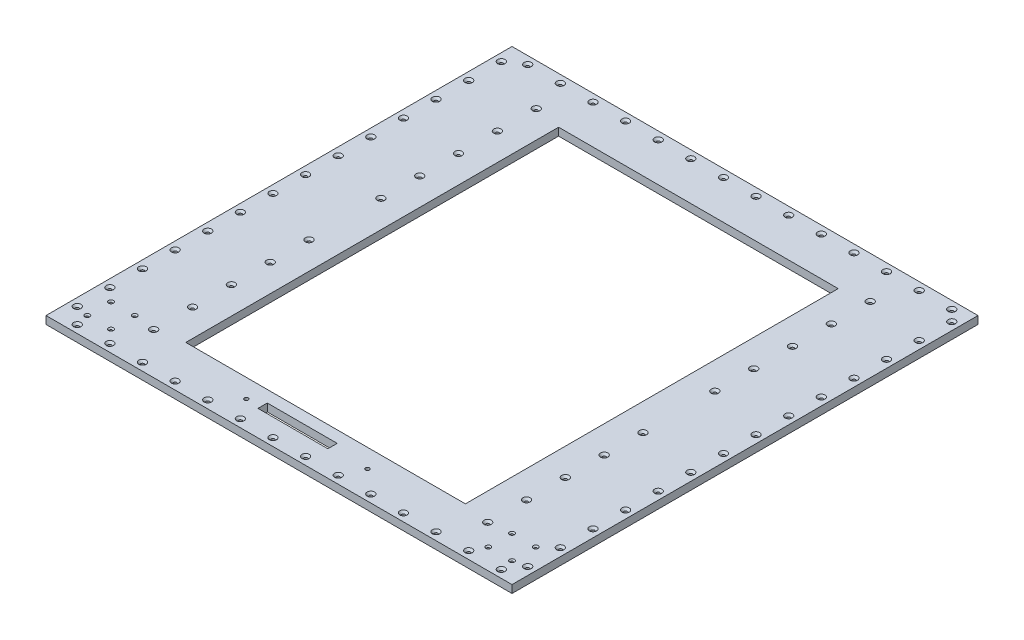
SolidWorks part; units mm, degrees
ref_plane "Płaszczyzna przednia" through (0, 0, 0) normal (0, 0, 1) x (1, 0, 0)
ref_plane "Płaszczyzna górna" through (0, 0, 0) normal (0, 1, 0) x (1, 0, 0)
ref_plane "Płaszczyzna prawa" through (0, 0, 0) normal (1, 0, 0) x (0, 0, -1)
sketch "Sketch1" plane through (0, 0, 0) normal (0, 1, 0) x (1, 0, 0)
  line L1 (0, 0) -> (600, 0)
  line L2 (0, 0) -> (0, 600)
  line L3 (0, 600) -> (600, 600)
  line L4 (600, 0) -> (600, 600)
  line L5 (0, 0) -> (600, 600) construction
  line L6 (0, 600) -> (600, 0) construction
  point P4 (300, 300)
  dimension "D1" = 600
  dimension "D2" = 600
extrude "Boss-Extrude1" add sketch "Sketch1" along normal blind 10
hole_wizard "CSK for M4 Flat Head Machine Screw1" positions "Sketch2" profile "Sketch3" countersink size "M4" standard "ANSI Metric" end condition through all
sketch "Sketch2" plane through (0, 10, 0) normal (0, 1, 0) x (1, 0, 0)
  line L0 (0, 0) -> (600, 0) construction
  line L1 (0, 600) -> (0, 0) construction
  line L2 (600, 0) -> (600, 600) construction
  point P0 (30.25, 10)
  point P14 (72.25, 10)
  point P15 (114.25, 10)
  point P16 (156.25, 10)
  point P17 (198.25, 10)
  point P18 (240.25, 10)
  point P19 (282.25, 10)
  point P20 (324.25, 10)
  point P21 (366.25, 10)
  point P22 (408.25, 10)
  point P23 (450.25, 10)
  point P24 (492.25, 10)
  point P25 (534.25, 10)
  point P26 (576.25, 10)
  point P27 (72.25, 590)
  point P28 (114.25, 590)
  point P29 (156.25, 590)
  point P30 (198.25, 590)
  point P31 (240.25, 590)
  point P32 (282.25, 590)
  point P33 (324.25, 590)
  point P34 (366.25, 590)
  point P35 (408.25, 590)
  point P36 (450.25, 590)
  point P37 (492.25, 590)
  point P38 (534.25, 590)
  point P39 (576.25, 590)
  point P40 (30.25, 590)
  point P42 (590, 30.25)
  point P59 (10, 30.25)
  point P60 (10, 72.25)
  point P61 (10, 114.25)
  point P62 (10, 156.25)
  point P63 (10, 198.25)
  point P64 (10, 240.25)
  point P65 (10, 282.25)
  point P66 (10, 324.25)
  point P67 (10, 366.25)
  point P68 (10, 408.25)
  point P69 (10, 450.25)
  point P70 (10, 492.25)
  point P71 (10, 534.25)
  point P72 (10, 576.25)
  point P73 (590, 72.25)
  point P74 (590, 114.25)
  point P75 (590, 156.25)
  point P76 (590, 198.25)
  point P77 (590, 240.25)
  point P78 (590, 282.25)
  point P79 (590, 324.25)
  point P80 (590, 366.25)
  point P81 (590, 408.25)
  point P82 (590, 450.25)
  point P83 (590, 492.25)
  point P84 (590, 534.25)
  point P85 (590, 576.25)
  dimension "D1" = 10
  dimension "D2" = 30.25
  dimension "D5" = 10
  dimension "D6" = 30.25
  dimension "D3" = 14
  dimension "D4" = 2
  dimension "D7" = 2
  dimension "D8" = 14
sketch "Sketch3" plane through (30.25, 10, -10) normal (1, 0, 0) x (0, 0, 1)
  line L0 (0, 0) -> (0, 10)
  line L1 (0, 10) -> (2.15, 10)
  line L2 (2.15, 10) -> (2.15, 2.55)
  line L3 (2.15, 2.55) -> (4.7, 0)
  line L5 (4.7, 0) -> (0, 0)
  line L6 (-2.15, 2.55) -> (-4.7, 0) construction
  line L11 (0, -6.35) -> (0, 107.95) construction
  dimension "Thru Hole Dia." = 4.3
  dimension "Thru Hole Depth" = 10
  dimension "Near C'Sink Dia." = 9.4
  dimension "Near C'Sink Angle" = 90
hole_wizard "CSK for M4 Flat Head Machine Screw2" positions "Sketch4" profile "Sketch5" countersink size "M4" standard "ANSI Metric" end condition through all
sketch "Sketch4" plane through (0, 10, 0) normal (0, 1, 0) x (1, 0, 0)
  line L0 (0, 0) -> (600, 0) construction
  line L1 (0, 600) -> (0, 0) construction
  line L2 (600, 600) -> (0, 600) construction
  point P0 (84.93, 53.75)
  point P14 (514.93, 53.75)
  point P15 (514.93, 103.75)
  point P16 (514.93, 153.75)
  point P17 (514.93, 203.75)
  point P18 (514.93, 253.75)
  point P19 (84.93, 103.75)
  point P20 (84.93, 153.75)
  point P21 (84.93, 203.75)
  point P22 (84.93, 253.75)
  point P23 (84.93, 546.25)
  point P36 (514.93, 546.25)
  point P37 (514.93, 496.25)
  point P38 (514.93, 446.25)
  point P39 (514.93, 396.25)
  point P40 (514.93, 346.25)
  point P41 (84.93, 496.25)
  point P42 (84.93, 446.25)
  point P43 (84.93, 396.25)
  point P44 (84.93, 346.25)
  dimension "D1" = 53.75
  dimension "D2" = 84.93
  dimension "D5" = 53.75
  dimension "D6" = 84.93
  dimension "D3" = 2
  dimension "D4" = 5
  dimension "D7" = 2
  dimension "D8" = 5
sketch "Sketch5" plane through (84.93, 10, -53.75) normal (1, 0, 0) x (0, 0, 1)
  line L0 (0, 0) -> (0, 10)
  line L1 (0, 10) -> (2.15, 10)
  line L2 (2.15, 10) -> (2.15, 2.55)
  line L3 (2.15, 2.55) -> (4.7, 0)
  line L5 (4.7, 0) -> (0, 0)
  line L6 (-2.15, 2.55) -> (-4.7, 0) construction
  line L11 (0, -6.35) -> (0, 107.95) construction
  dimension "Thru Hole Dia." = 4.3
  dimension "Thru Hole Depth" = 10
  dimension "Near C'Sink Dia." = 9.4
  dimension "Near C'Sink Angle" = 90
sketch "Sketch6" plane through (0, 10, 0) normal (0, 1, 0) x (1, 0, 0)
  line L0 (0, 600) -> (0, 0) construction
  line L1 (120, 540) -> (480, 540)
  line L2 (120, 540) -> (120, 60)
  line L3 (120, 60) -> (480, 60)
  line L4 (480, 540) -> (480, 60)
  line L5 (120, 540) -> (480, 60) construction
  line L6 (120, 60) -> (480, 540) construction
  line L7 (600, 0) -> (600, 600) construction
  line L8 (0, 0) -> (600, 0) construction
  line L9 (600, 600) -> (0, 600) construction
  point P4 (300, 300)
  dimension "D1" = 120
  dimension "D2" = 120
  dimension "D3" = 60
  dimension "D4" = 60
extrude "Cut-Extrude1" cut sketch "Sketch6" against normal blind 10
sketch "Sketch7" plane through (0, 0, 0) normal (0, -1, 0) x (1, 0, 0)
  line L0 (600, -600) -> (0, -600) construction
  line L1 (72, -535) -> (58, -535)
  line L2 (72, -535) -> (72, -65)
  line L3 (72, -65) -> (58, -65)
  line L4 (58, -535) -> (58, -65)
  line L5 (72, -535) -> (58, -65) construction
  line L6 (72, -65) -> (58, -535) construction
  line L7 (0, -600) -> (0, 0) construction
  line L8 (112, -535) -> (112, -65)
  line L9 (112, -535) -> (98, -535)
  line L10 (98, -535) -> (98, -65)
  line L11 (112, -65) -> (98, -65)
  line L12 (542, -535) -> (542, -65)
  line L13 (542, -65) -> (528, -65)
  line L14 (528, -535) -> (528, -65)
  line L15 (542, -535) -> (528, -535)
  line L16 (502, -65) -> (488, -535) construction
  line L17 (502, -535) -> (502, -65)
  line L18 (502, -535) -> (488, -535)
  line L19 (488, -535) -> (488, -65)
  line L20 (502, -65) -> (488, -65)
  point P4 (65, -300)
  dimension "D1" = 65
  dimension "D2" = 470
  dimension "D3" = 14
  dimension "D4" = 72
  dimension "D5" = 2
  dimension "D6" = 2
extrude "Cut-Extrude2" cut sketch "Sketch7" against normal blind 2
chamfer "Chamfer1" distance 2 angle 45 16 edges at (65, 2, -535) (58, 2, -300) (65, 2, -65) (72, 2, -300) (98, 2, -300) (105, 2, -65) (112, 2, -300) (105, 2, -535) (488, 2, -300) (495, 2, -65) (502, 2, -300) (495, 2, -535) (528, 2, -300) (535, 2, -65) (542, 2, -300) (535, 2, -535)
sketch "Sketch8" plane through (0, 0, 0) normal (0, -1, 0) x (1, 0, 0)
  line L0 (600, 0) -> (600, -600) construction
  line L1 (20, -600) -> (580, -600) construction
  circle A0 centre (558, -558) radius 5
  dimension "D1" = 10
  dimension "D2" = 42
  dimension "D3" = 42
extrude "Cut-Extrude3" cut sketch "Sketch8" against normal blind 5
hole_wizard "CSK for M3 Flat Head Machine Screw1" positions "Sketch9" profile "Sketch10" countersink size "M3" standard "ANSI Metric" end condition through all
sketch "Sketch9" plane through (0, 10, 0) normal (0, 1, 0) x (1, 0, 0)
  line L0 (600, 0) -> (600, 600) construction
  line L1 (0, 0) -> (600, 0) construction
  line L7 (300, 0) -> (300, 600) construction
  line L8 (600, 600) -> (0, 600) construction
  point P0 (542.9, 57.1)
  point P2 (573.4, 57.1)
  point P4 (573.4, 26.6)
  point P6 (542.9, 26.6)
  point P35 (57.1, 26.6)
  point P36 (26.6, 26.6)
  point P37 (26.6, 57.1)
  point P38 (57.1, 57.1)
  dimension "D1" = 57.1
  dimension "D2" = 26.6
  dimension "D3" = 30.5
  dimension "D4" = 30.5
  dimension "D5" = 600
  dimension "D6" = 300
sketch "Sketch10" plane through (542.9, 10, -57.1) normal (1, 0, 0) x (0, 0, 1)
  line L0 (0, 0) -> (0, 10)
  line L1 (0, 10) -> (1.6, 10)
  line L2 (1.6, 10) -> (1.6, 1.55)
  line L3 (1.6, 1.55) -> (3.15, 0)
  line L5 (3.15, 0) -> (0, 0)
  line L6 (-1.6, 1.55) -> (-3.15, 0) construction
  line L11 (0, -6.35) -> (0, 107.95) construction
  dimension "Thru Hole Dia." = 3.2
  dimension "Thru Hole Depth" = 10
  dimension "Near C'Sink Dia." = 6.3
  dimension "Near C'Sink Angle" = 90
sketch "Sketch11" plane through (0, 0, 0) normal (0, -1, 0) x (1, 0, 0)
  line L0 (0, -600) -> (0, 0) construction
  line L1 (600, -600) -> (0, -600) construction
  circle A0 centre (42, -558) radius 5
  dimension "D1" = 10
  dimension "D2" = 42
  dimension "D3" = 42
extrude "Cut-Extrude4" cut sketch "Sketch11" against normal blind 5
sketch "Sketch12" plane through (0, 0, 0) normal (0, -1, 0) x (1, 0, 0)
  line L0 (600, -600) -> (0, -600) construction
  line L1 (600, 0) -> (600, -600) construction
  circle A0 centre (425, -558) radius 4
  dimension "D1" = 42
  dimension "D2" = 8
  dimension "D3" = 175
extrude "Cut-Extrude5" cut sketch "Sketch12" against normal blind 5
sketch "Sketch13" plane through (0, 0, 0) normal (0, -1, 0) x (-1, 0, 0)
  line L0 (-600, 600) -> (0, 600) construction
  line L1 (0, 20) -> (0, 580) construction
  circle A0 centre (-175, 558) radius 4
  dimension "D1" = 42
  dimension "D2" = 175
  dimension "D3" = 8
extrude "Cut-Extrude6" cut sketch "Sketch13" against normal blind 5
sketch "Sketch14" plane through (0, -560, 0) normal (0, 1, 0) x (1, 0, 0)
  line L0 (0, 600) -> (600, 600) construction
  line L1 (0, 0) -> (0, 600) construction
  circle A0 centre (175, 558) radius 4
  dimension "D1" = 42
  dimension "D2" = 175
  dimension "D3" = 8
hole_wizard "Ø5.0mm Dowel Hole1" positions "Sketch15" profile "Sketch16" hole size "Ø5.0" standard "ANSI Metric" end condition up to next
sketch "Sketch15" plane through (0, 10, 0) normal (0, 1, 0) x (1, 0, 0)
  point P0 (222, 35.9)
  point P3 (378, 35.9)
sketch "Sketch16" plane through (222, 10, -35.9) normal (1, 0, 0) x (0, 0, 1)
  line L0 (0, 0) -> (0, 10)
  line L1 (0, 10) -> (2.5, 10)
  line L2 (2.5, 10) -> (2.5, 0)
  line L5 (2.5, 0) -> (0, 0)
  line L11 (0, -6.35) -> (0, 107.95) construction
  dimension "Thru Hole Dia." = 5
  dimension "Thru Hole Depth" = 10
sketch "Sketch17" plane through (0, 10, 0) normal (0, 1, 0) x (1, 0, 0)
  line L0 (120, 60) -> (480, 60) construction
  line L1 (240, 44.9) -> (330, 44.9)
  line L2 (240, 44.9) -> (240, 32.9)
  line L3 (240, 32.9) -> (330, 32.9)
  line L4 (330, 44.9) -> (330, 32.9)
  line L5 (240, 44.9) -> (330, 32.9) construction
  line L6 (240, 32.9) -> (330, 44.9) construction
  line L7 (600, 0) -> (600, 600) construction
  line L8 (0, 0) -> (0, 600) construction
  point P4 (285, 38.9)
  dimension "D1" = 15.1
  dimension "D2" = 12
  dimension "D3" = 270
  dimension "D4" = 240
extrude "Cut-Extrude7" cut sketch "Sketch17" against normal blind 10
